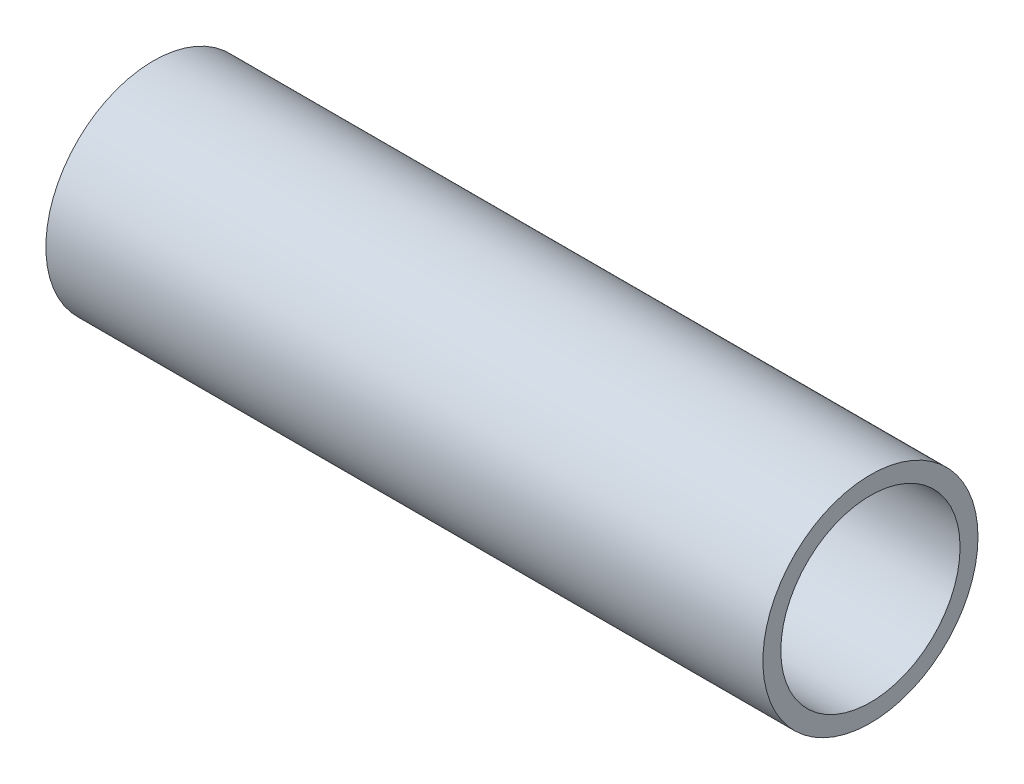
SolidWorks part; units mm, degrees
material "7075-O (SS)"
ref_plane "Front Plane" through (0, 0, 0) normal (0, 0, 1) x (1, 0, 0)
ref_plane "Top Plane" through (0, 0, 0) normal (0, 1, 0) x (1, 0, 0)
ref_plane "Right Plane" through (0, 0, 0) normal (1, 0, 0) x (0, 0, -1)
sketch "Sketch1" plane through (0, 0, 0) normal (1, 0, 0) x (0, 0, -1)
  circle A0 centre (0, 0) radius 1.5875
  circle A1 centre (0, 0) radius 1.905
  dimension "D1" = 3.175
  dimension "D2" = 0.3175
extrude "Boss-Extrude1" add sketch "Sketch1" along normal blind 12.7
ref_axis "Axis1" through (12.7, 0, 0) along (-1, 0, 0)
